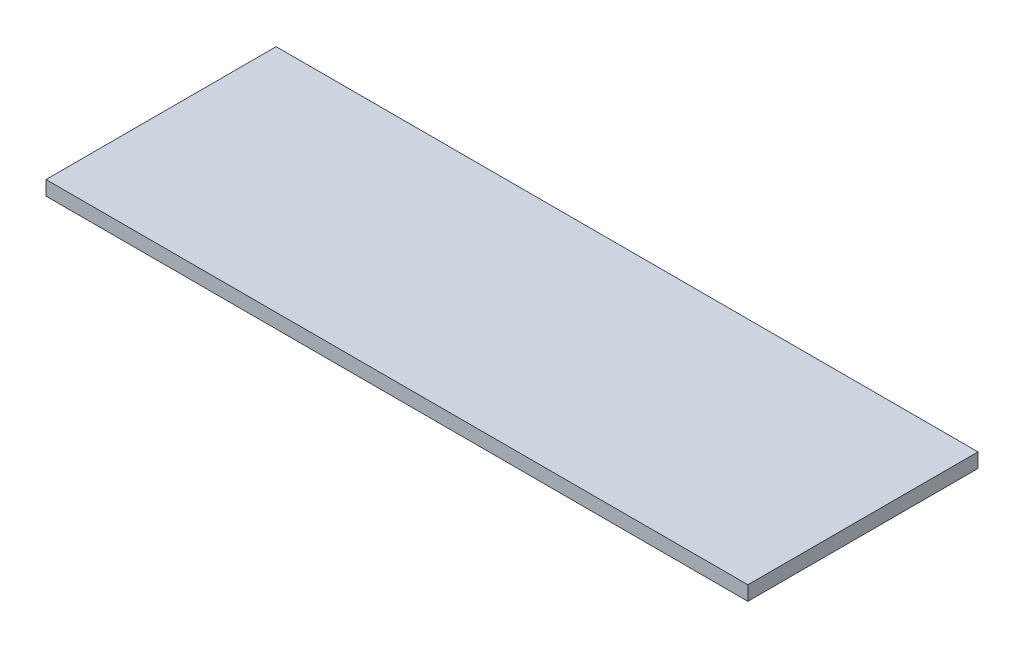
SolidWorks part; units mm, degrees
ref_plane "前视基准面" through (0, 0, 0) normal (0, 0, 1) x (1, 0, 0)
ref_plane "上视基准面" through (0, 0, 0) normal (0, 1, 0) x (1, 0, 0)
ref_plane "右视基准面" through (0, 0, 0) normal (1, 0, 0) x (0, 0, -1)
sketch "草图1" plane through (0, 0, 0) normal (0, 1, 0) x (1, 0, 0)
  line L1 (0, 0) -> (244, 0)
  line L2 (0, 0) -> (0, -80)
  line L3 (0, -80) -> (244, -80)
  line L4 (244, 0) -> (244, -80)
  dimension "D1" = 244
  dimension "D2" = 80
extrude "凸台-拉伸1" add sketch "草图1" along normal blind 5
